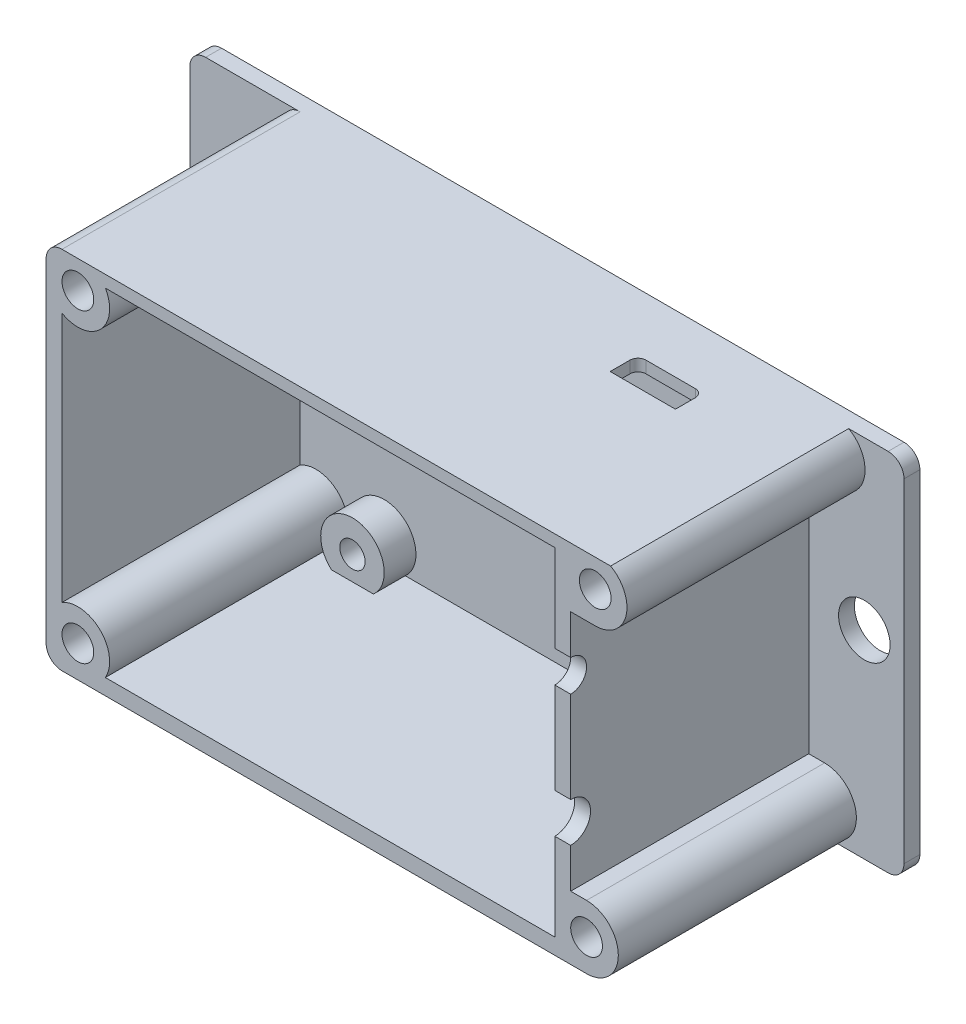
SolidWorks part; units mm, degrees
ref_plane "前视基准面" through (0, 0, 0) normal (0, 0, 1) x (1, 0, 0)
ref_plane "上视基准面" through (0, 0, 0) normal (0, 1, 0) x (1, 0, 0)
ref_plane "右视基准面" through (0, 0, 0) normal (1, 0, 0) x (0, 0, -1)
sketch "Model" plane through (0, 0, 0) normal (0, 0, 1) x (1, 0, 0)
  line L0 (0, 2.26) -> (0, 39.4058)
  line L1 (2.4326, 41.5) -> (50.1564, 41.5)
  line L2 (52.5, 39.422) -> (52.5, 2.28)
  line L3 (50.22, 0) -> (2.26, 0)
  line L4 (0.57, 8.85) -> (-6.93, 8.85)
  line L5 (-6.93, 8.85) -> (-6.93, 24.85)
  line L6 (-6.93, 24.85) -> (0.57, 24.85)
  line L7 (16.57, 8.85) -> (17.57, 8.85)
  line L8 (17.57, 8.85) -> (17.57, 10.85)
  line L9 (17.57, 22.85) -> (17.57, 24.85)
  line L10 (17.57, 24.85) -> (16.57, 24.85)
  line L11 (24.196, 8.775) -> (23.307, 8.775)
  line L12 (22.926, 9.156) -> (22.926, 9.664)
  line L13 (23.307, 10.045) -> (24.196, 10.045)
  line L14 (24.704, 10.045) -> (25.593, 10.045)
  line L15 (25.974, 9.664) -> (25.974, 9.156)
  line L16 (25.593, 8.775) -> (24.704, 8.775)
  line L17 (34.756, 17.315) -> (33.867, 17.315)
  line L18 (33.486, 17.696) -> (33.486, 18.204)
  line L19 (33.867, 18.585) -> (34.756, 18.585)
  line L20 (35.264, 18.585) -> (36.153, 18.585)
  line L21 (36.534, 18.204) -> (36.534, 17.696)
  line L22 (36.153, 17.315) -> (35.264, 17.315)
  line L23 (16.835, 4.806) -> (16.835, 3.917)
  line L24 (16.454, 3.536) -> (15.946, 3.536)
  line L25 (15.565, 3.917) -> (15.565, 4.806)
  line L26 (15.565, 5.314) -> (15.565, 6.203)
  line L27 (15.946, 6.584) -> (16.454, 6.584)
  line L28 (16.835, 6.203) -> (16.835, 5.314)
  line L29 (26.454, 3.425) -> (27.343, 3.425)
  line L30 (27.724, 3.044) -> (27.724, 2.536)
  line L31 (27.343, 2.155) -> (26.454, 2.155)
  line L32 (25.946, 2.155) -> (25.057, 2.155)
  line L33 (24.676, 2.536) -> (24.676, 3.044)
  line L34 (25.057, 3.425) -> (25.946, 3.425)
  line L35 (18.255, 4.756) -> (18.255, 3.867)
  line L36 (17.874, 3.486) -> (17.366, 3.486)
  line L37 (16.985, 3.867) -> (16.985, 4.756)
  line L38 (16.985, 5.264) -> (16.985, 6.153)
  line L39 (17.366, 6.534) -> (17.874, 6.534)
  line L40 (18.255, 6.153) -> (18.255, 5.264)
  line L41 (12.8, 35.75) -> (12.8, 38.8)
  line L42 (12.8, 38.8) -> (14.05, 39.95)
  line L43 (14.05, 39.95) -> (16.45, 39.95)
  line L44 (16.45, 39.95) -> (17.6, 38.9)
  line L45 (17.6, 38.9) -> (17.6, 35.7)
  line L46 (17.6, 35.7) -> (16.45, 34.65)
  line L47 (16.45, 34.65) -> (14, 34.65)
  line L48 (14, 34.65) -> (12.8, 35.75)
  line L49 (3.87, 5.53) -> (6.67, 5.53)
  line L50 (6.67, 5.53) -> (6.67, 4.13)
  line L51 (6.67, 4.13) -> (3.87, 4.13)
  line L52 (3.87, 4.13) -> (3.87, 5.53)
  line L53 (20.8, 6.56) -> (20.8, 9.36)
  line L54 (20.8, 9.36) -> (22.2, 9.36)
  line L55 (22.2, 9.36) -> (22.2, 6.56)
  line L56 (22.2, 6.56) -> (20.8, 6.56)
  line L57 (8.21, 6.97) -> (8.21, 4.17)
  line L58 (8.21, 4.17) -> (6.81, 4.17)
  line L59 (6.81, 4.17) -> (6.81, 6.97)
  line L60 (6.81, 6.97) -> (8.21, 6.97)
  line L61 (10.82, 29.94) -> (10.82, 27.14)
  line L62 (10.82, 27.14) -> (9.42, 27.14)
  line L63 (9.42, 27.14) -> (9.42, 29.94)
  line L64 (9.42, 29.94) -> (10.82, 29.94)
  line L65 (33.69, 12.87) -> (30.89, 12.87)
  line L66 (30.89, 12.87) -> (30.89, 14.27)
  line L67 (30.89, 14.27) -> (33.69, 14.27)
  line L68 (33.69, 14.27) -> (33.69, 12.87)
  line L69 (14.93, 29.94) -> (14.93, 27.14)
  line L70 (14.93, 27.14) -> (13.53, 27.14)
  line L71 (13.53, 27.14) -> (13.53, 29.94)
  line L72 (13.53, 29.94) -> (14.93, 29.94)
  line L73 (26.13, 4.53) -> (26.37, 4.53)
  line L74 (26.37, 4.53) -> (26.37, 7.36)
  line L75 (26.37, 7.36) -> (26.13, 7.36)
  line L76 (22.89, 4.53) -> (22.6, 4.53)
  line L77 (22.6, 4.53) -> (22.6, 7.37)
  line L78 (22.6, 7.37) -> (22.87, 7.37)
  line L79 (1.79, 29.79) -> (6.87, 29.79)
  line L80 (6.87, 29.79) -> (6.87, 27.25)
  line L81 (6.87, 27.25) -> (1.79, 27.25)
  line L82 (1.79, 27.25) -> (1.79, 29.79)
  line L83 (29.996, 38.955) -> (29.107, 38.955)
  line L84 (28.726, 39.336) -> (28.726, 39.844)
  line L85 (29.107, 40.225) -> (29.996, 40.225)
  line L86 (30.504, 40.225) -> (31.393, 40.225)
  line L87 (31.774, 39.844) -> (31.774, 39.336)
  line L88 (31.393, 38.955) -> (30.504, 38.955)
  line L89 (35.825, 11.706) -> (35.825, 10.817)
  line L90 (35.444, 10.436) -> (34.936, 10.436)
  line L91 (34.555, 10.817) -> (34.555, 11.706)
  line L92 (34.555, 12.214) -> (34.555, 13.103)
  line L93 (34.936, 13.484) -> (35.444, 13.484)
  line L94 (35.825, 13.103) -> (35.825, 12.214)
  line L95 (31.416, 6.905) -> (30.527, 6.905)
  line L96 (30.146, 7.286) -> (30.146, 7.794)
  line L97 (30.527, 8.175) -> (31.416, 8.175)
  line L98 (31.924, 8.175) -> (32.813, 8.175)
  line L99 (33.194, 7.794) -> (33.194, 7.286)
  line L100 (32.813, 6.905) -> (31.924, 6.905)
  line L101 (27.125, 13.384) -> (27.125, 14.273)
  line L102 (27.506, 14.654) -> (28.014, 14.654)
  line L103 (28.395, 14.273) -> (28.395, 13.384)
  line L104 (28.395, 12.876) -> (28.395, 11.987)
  line L105 (28.014, 11.606) -> (27.506, 11.606)
  line L106 (27.125, 11.987) -> (27.125, 12.876)
  line L107 (2.726, 5.765) -> (1.837, 5.765)
  line L108 (1.456, 6.146) -> (1.456, 6.654)
  line L109 (1.837, 7.035) -> (2.726, 7.035)
  line L110 (3.234, 7.035) -> (4.123, 7.035)
  line L111 (4.504, 6.654) -> (4.504, 6.146)
  line L112 (4.123, 5.765) -> (3.234, 5.765)
  line L113 (38.274, 36.345) -> (39.163, 36.345)
  line L114 (39.544, 35.964) -> (39.544, 35.456)
  line L115 (39.163, 35.075) -> (38.274, 35.075)
  line L116 (37.766, 35.075) -> (36.877, 35.075)
  line L117 (36.496, 35.456) -> (36.496, 35.964)
  line L118 (36.877, 36.345) -> (37.766, 36.345)
  line L119 (35.295, 38.504) -> (35.295, 39.393)
  line L120 (35.676, 39.774) -> (36.184, 39.774)
  line L121 (36.565, 39.393) -> (36.565, 38.504)
  line L122 (36.565, 37.996) -> (36.565, 37.107)
  line L123 (36.184, 36.726) -> (35.676, 36.726)
  line L124 (35.295, 37.107) -> (35.295, 37.996)
  line L125 (31.265, 4.376) -> (31.265, 3.487)
  line L126 (30.884, 3.106) -> (30.376, 3.106)
  line L127 (29.995, 3.487) -> (29.995, 4.376)
  line L128 (29.995, 4.884) -> (29.995, 5.773)
  line L129 (30.376, 6.154) -> (30.884, 6.154)
  line L130 (31.265, 5.773) -> (31.265, 4.884)
  line L131 (33.42, 4.7325) -> (33.42, 6.15)
  line L132 (33.42, 6.15) -> (31.5, 6.15)
  line L133 (31.5, 6.15) -> (31.5, 4.7325)
  line L134 (33.42, 2.8275) -> (33.42, 1.43)
  line L135 (33.42, 1.43) -> (31.5, 1.43)
  line L136 (31.5, 1.43) -> (31.5, 2.8275)
  line L137 (37.99, 12.2925) -> (37.99, 13.71)
  line L138 (37.99, 13.71) -> (36.07, 13.71)
  line L139 (36.07, 13.71) -> (36.07, 12.2925)
  line L140 (37.99, 10.3875) -> (37.99, 8.99)
  line L141 (37.99, 8.99) -> (36.07, 8.99)
  line L142 (36.07, 8.99) -> (36.07, 10.3875)
  line L143 (37.074, 38.3336) -> (37.074, 37.343)
  line L144 (37.582, 36.835) -> (38.6488, 36.835)
  line L145 (39.106, 37.3176) -> (39.106, 38.3336)
  line L146 (37.074, 39.1464) -> (37.074, 40.137)
  line L147 (37.582, 40.645) -> (38.6488, 40.645)
  line L148 (39.106, 40.1624) -> (39.106, 39.1464)
  line L149 (33.975, 16.983) -> (31.689, 16.983)
  line L150 (31.689, 16.983) -> (31.689, 14.697)
  line L151 (31.689, 14.697) -> (33.975, 14.697)
  line L152 (35.245, 16.983) -> (37.15, 16.983)
  line L153 (37.15, 16.983) -> (37.531, 16.602)
  line L154 (37.531, 16.602) -> (37.531, 15.078)
  line L155 (37.531, 15.078) -> (37.15, 14.697)
  line L156 (37.15, 14.697) -> (35.245, 14.697)
  line L157 (21.1, 35.75) -> (21.1, 38.8)
  line L158 (21.1, 38.8) -> (22.35, 39.95)
  line L159 (22.35, 39.95) -> (24.75, 39.95)
  line L160 (24.75, 39.95) -> (25.9, 38.9)
  line L161 (25.9, 38.9) -> (25.9, 35.7)
  line L162 (25.9, 35.7) -> (24.75, 34.65)
  line L163 (24.75, 34.65) -> (22.3, 34.65)
  line L164 (22.3, 34.65) -> (21.1, 35.75)
  line L165 (5.44, 35.75) -> (5.44, 38.8)
  line L166 (5.44, 38.8) -> (6.69, 39.95)
  line L167 (6.69, 39.95) -> (9.09, 39.95)
  line L168 (9.09, 39.95) -> (10.24, 38.9)
  line L169 (10.24, 38.9) -> (10.24, 35.7)
  line L170 (10.24, 35.7) -> (9.09, 34.65)
  line L171 (9.09, 34.65) -> (6.64, 34.65)
  line L172 (6.64, 34.65) -> (5.44, 35.75)
  line L173 (34.57, 3.22) -> (38.57, 3.22)
  line L174 (38.57, 3.22) -> (38.57, 8.72)
  line L175 (38.57, 8.72) -> (34.57, 8.72)
  line L176 (34.57, 8.72) -> (34.57, 3.22)
  line L177 (39.81, 30.07) -> (37.01, 30.07)
  line L178 (37.01, 30.07) -> (37.01, 31.47)
  line L179 (37.01, 31.47) -> (39.81, 31.47)
  line L180 (39.81, 31.47) -> (39.81, 30.07)
  line L181 (28.51, 40.17) -> (28.51, 37.37)
  line L182 (28.51, 37.37) -> (27.11, 37.37)
  line L183 (27.11, 37.37) -> (27.11, 40.17)
  line L184 (27.11, 40.17) -> (28.51, 40.17)
  line L185 (32.06, 40.25) -> (34.86, 40.25)
  line L186 (34.86, 40.25) -> (34.86, 38.85)
  line L187 (34.86, 38.85) -> (32.06, 38.85)
  line L188 (32.06, 38.85) -> (32.06, 40.25)
  line L189 (28.56, 11.71) -> (28.56, 14.51)
  line L190 (28.56, 14.51) -> (29.96, 14.51)
  line L191 (29.96, 14.51) -> (29.96, 11.71)
  line L192 (29.96, 11.71) -> (28.56, 11.71)
  line L193 (25.54, 13.29) -> (25.54, 16.09)
  line L194 (25.54, 16.09) -> (26.94, 16.09)
  line L195 (26.94, 16.09) -> (26.94, 13.29)
  line L196 (26.94, 13.29) -> (25.54, 13.29)
  line L197 (27.11, 11.4) -> (29.91, 11.4)
  line L198 (29.91, 11.4) -> (29.91, 10)
  line L199 (29.91, 10) -> (27.11, 10)
  line L200 (27.11, 10) -> (27.11, 11.4)
  line L201 (29.06, 8.4) -> (26.26, 8.4)
  line L202 (26.26, 8.4) -> (26.26, 9.8)
  line L203 (26.26, 9.8) -> (29.06, 9.8)
  line L204 (29.06, 9.8) -> (29.06, 8.4)
  line L205 (18.53, 32.56) -> (18.53, 29.76)
  line L206 (18.53, 29.76) -> (17.13, 29.76)
  line L207 (17.13, 29.76) -> (17.13, 32.56)
  line L208 (17.13, 32.56) -> (18.53, 32.56)
  line L209 (5.02, 31.95) -> (2.22, 31.95)
  line L210 (2.22, 31.95) -> (2.22, 33.35)
  line L211 (2.22, 33.35) -> (5.02, 33.35)
  line L212 (5.02, 33.35) -> (5.02, 31.95)
  line L213 (9.22, 29.96) -> (9.22, 27.16)
  line L214 (9.22, 27.16) -> (7.82, 27.16)
  line L215 (7.82, 27.16) -> (7.82, 29.96)
  line L216 (7.82, 29.96) -> (9.22, 29.96)
  line L217 (25.54, 18.87) -> (28.34, 18.87)
  line L218 (28.34, 18.87) -> (28.34, 17.47)
  line L219 (28.34, 17.47) -> (25.54, 17.47)
  line L220 (25.54, 17.47) -> (25.54, 18.87)
  line L221 (28.31, 19.13) -> (25.51, 19.13)
  line L222 (25.51, 19.13) -> (25.51, 20.53)
  line L223 (25.51, 20.53) -> (28.31, 20.53)
  line L224 (28.31, 20.53) -> (28.31, 19.13)
  line L225 (8.87, 4.41) -> (8.87, 7.21)
  line L226 (8.87, 7.21) -> (10.27, 7.21)
  line L227 (10.27, 7.21) -> (10.27, 4.41)
  line L228 (10.27, 4.41) -> (8.87, 4.41)
  line L229 (11.05, 4.16) -> (11.05, 6.96)
  line L230 (11.05, 6.96) -> (12.45, 6.96)
  line L231 (12.45, 6.96) -> (12.45, 4.16)
  line L232 (12.45, 4.16) -> (11.05, 4.16)
  line L233 (7.61, 30.34) -> (4.81, 30.34)
  line L234 (4.81, 30.34) -> (4.81, 31.74)
  line L235 (4.81, 31.74) -> (7.61, 31.74)
  line L236 (7.61, 31.74) -> (7.61, 30.34)
  line L237 (4.24, 30.32) -> (1.44, 30.32)
  line L238 (1.44, 30.32) -> (1.44, 31.72)
  line L239 (1.44, 31.72) -> (4.24, 31.72)
  line L240 (4.24, 31.72) -> (4.24, 30.32)
  line L241 (39.81, 31.61) -> (37.01, 31.61)
  line L242 (37.01, 31.61) -> (37.01, 33.01)
  line L243 (37.01, 33.01) -> (39.81, 33.01)
  line L244 (39.81, 33.01) -> (39.81, 31.61)
  line L245 (30.83, 8.94) -> (30.83, 8.7)
  line L246 (30.83, 8.7) -> (33.66, 8.7)
  line L247 (33.66, 8.7) -> (33.66, 8.94)
  line L248 (30.83, 12.18) -> (30.83, 12.47)
  line L249 (30.83, 12.47) -> (33.67, 12.47)
  line L250 (33.67, 12.47) -> (33.67, 12.2)
  line L251 (51.33, 22.79) -> (51.33, 33.29)
  line L252 (51.33, 33.29) -> (45.93, 33.29)
  line L253 (45.93, 33.29) -> (45.93, 22.79)
  line L254 (45.93, 22.79) -> (46.63, 22.09)
  line L255 (46.63, 22.09) -> (50.63, 22.09)
  line L256 (50.63, 22.09) -> (51.33, 22.79)
  line L257 (48.63, 35.31) -> (48.63, 33.278)
  line L258 (49.646, 34.294) -> (47.614, 34.294)
  line L259 (51.38, 7.21) -> (51.38, 17.71)
  line L260 (51.38, 17.71) -> (45.98, 17.71)
  line L261 (45.98, 17.71) -> (45.98, 7.21)
  line L262 (45.98, 7.21) -> (46.68, 6.51)
  line L263 (46.68, 6.51) -> (50.68, 6.51)
  line L264 (50.68, 6.51) -> (51.38, 7.21)
  line L265 (48.68, 19.73) -> (48.68, 17.698)
  line L266 (49.696, 18.714) -> (47.664, 18.714)
  line L267 (31.402, 24.62) -> (31.402, 19.54)
  line L268 (31.402, 19.54) -> (34.958, 19.54)
  line L269 (34.958, 19.54) -> (34.958, 24.62)
  line L270 (34.958, 24.62) -> (31.402, 24.62)
  line L271 (33.942, 24.62) -> (33.942, 24.112)
  line L272 (33.942, 24.112) -> (32.418, 24.112)
  line L273 (32.418, 24.112) -> (32.418, 24.62)
  line L274 (35.323, 25.5545) -> (37.482, 25.5545)
  line L275 (37.482, 25.5545) -> (37.482, 29.7455)
  line L276 (37.482, 29.7455) -> (35.323, 29.7455)
  line L277 (30.497, 25.5545) -> (28.338, 25.5545)
  line L278 (28.338, 25.5545) -> (28.338, 29.7455)
  line L279 (28.338, 29.7455) -> (30.497, 29.7455)
  line L280 (39.675, 36.4523) -> (39.675, 38.9337)
  line L281 (39.675, 38.9337) -> (39.6757, 38.9337)
  line L282 (39.6757, 38.9337) -> (39.6757, 41.34)
  line L283 (39.6757, 41.34) -> (47.0987, 41.34)
  line L284 (47.0987, 41.34) -> (47.0987, 36.4523)
  line L285 (47.0987, 36.4523) -> (39.675, 36.4523)
  line L286 (39.674, 41.32) -> (47.0987, 41.32)
  line L287 (47.0987, 41.32) -> (47.0987, 41.84)
  line L288 (47.0987, 41.84) -> (39.674, 41.84)
  line L289 (39.674, 41.84) -> (39.674, 41.32)
  line L290 (40.55, 41.34) -> (40.12, 41.77)
  line L291 (46.28, 41.37) -> (46.71, 41.8)
  line L292 (35.28, 32.52) -> (35.28, 31.92)
  line L293 (35.28, 31.92) -> (34.88, 31.52)
  line L294 (34.88, 31.52) -> (34.38, 31.52)
  line L295 (34.98, 36.32) -> (34.98, 36.82)
  line L296 (34.98, 36.82) -> (34.48, 36.82)
  line L297 (29.98, 36.32) -> (29.98, 36.82)
  line L298 (29.98, 36.82) -> (30.48, 36.82)
  line L299 (29.98, 32.32) -> (29.98, 31.82)
  line L300 (29.98, 31.82) -> (30.48, 31.82)
  arc A0 (0, 2.26) -> (2.26, 0) centre (2.5947, 2.5947) ccw
  arc A1 (2.4326, 41.5) -> (0, 39.4058) centre (2.365, 39.1186) ccw
  arc A2 (52.5, 39.422) -> (50.1564, 41.5) centre (50.2928, 39.2933) ccw
  arc A3 (50.22, 0) -> (52.5, 2.28) centre (50.2397, 2.2603) ccw
  circle A4 centre (2.26, 0) radius 0.0635
  circle A5 centre (0, 2.26) radius 0.0635
  circle A6 centre (0, 39.4058) radius 0.0635
  circle A7 centre (2.4326, 41.5) radius 0.0635
  circle A8 centre (50.1564, 41.5) radius 0.0635
  circle A9 centre (52.5, 39.422) radius 0.0635
  circle A10 centre (52.5, 2.28) radius 0.0635
  circle A11 centre (2, 39.5) radius 1.1
  circle A12 centre (50.5, 39.5) radius 1.1
  circle A13 centre (50.5, 2) radius 1.1
  circle A14 centre (2, 2) radius 1.1
  circle A15 centre (0.57, 8.85) radius 0.0635
  circle A16 centre (-6.93, 8.85) radius 0.0635
  circle A17 centre (-6.93, 24.85) radius 0.0635
  circle A18 centre (0.57, 24.85) radius 0.0635
  circle A19 centre (16.57, 8.85) radius 0.0635
  circle A20 centre (17.57, 8.85) radius 0.0635
  circle A21 centre (17.57, 10.85) radius 0.0635
  circle A22 centre (17.57, 22.85) radius 0.0635
  circle A23 centre (17.57, 24.85) radius 0.0635
  circle A24 centre (16.57, 24.85) radius 0.0635
  circle A25 centre (1.57, 7.55) radius 0.3606
  arc A26 (22.926, 9.156) -> (23.307, 8.775) centre (23.307, 9.156) ccw
  arc A27 (23.307, 10.045) -> (22.926, 9.664) centre (23.307, 9.664) ccw
  circle A28 centre (24.196, 8.775) radius 0.025
  circle A29 centre (23.307, 8.775) radius 0.025
  arc A30 (25.974, 9.664) -> (25.593, 10.045) centre (25.593, 9.664) ccw
  arc A31 (25.593, 8.775) -> (25.974, 9.156) centre (25.593, 9.156) ccw
  circle A32 centre (24.704, 10.045) radius 0.025
  circle A33 centre (25.593, 10.045) radius 0.025
  arc A34 (33.486, 17.696) -> (33.867, 17.315) centre (33.867, 17.696) ccw
  arc A35 (33.867, 18.585) -> (33.486, 18.204) centre (33.867, 18.204) ccw
  circle A36 centre (34.756, 17.315) radius 0.025
  circle A37 centre (33.867, 17.315) radius 0.025
  arc A38 (36.534, 18.204) -> (36.153, 18.585) centre (36.153, 18.204) ccw
  arc A39 (36.153, 17.315) -> (36.534, 17.696) centre (36.153, 17.696) ccw
  circle A40 centre (35.264, 18.585) radius 0.025
  circle A41 centre (36.153, 18.585) radius 0.025
  arc A42 (16.454, 3.536) -> (16.835, 3.917) centre (16.454, 3.917) ccw
  arc A43 (15.565, 3.917) -> (15.946, 3.536) centre (15.946, 3.917) ccw
  circle A44 centre (16.835, 4.806) radius 0.025
  circle A45 centre (16.835, 3.917) radius 0.025
  arc A46 (15.946, 6.584) -> (15.565, 6.203) centre (15.946, 6.203) ccw
  arc A47 (16.835, 6.203) -> (16.454, 6.584) centre (16.454, 6.203) ccw
  circle A48 centre (15.565, 5.314) radius 0.025
  circle A49 centre (15.565, 6.203) radius 0.025
  arc A50 (27.724, 3.044) -> (27.343, 3.425) centre (27.343, 3.044) ccw
  arc A51 (27.343, 2.155) -> (27.724, 2.536) centre (27.343, 2.536) ccw
  circle A52 centre (26.454, 3.425) radius 0.025
  circle A53 centre (27.343, 3.425) radius 0.025
  arc A54 (24.676, 2.536) -> (25.057, 2.155) centre (25.057, 2.536) ccw
  arc A55 (25.057, 3.425) -> (24.676, 3.044) centre (25.057, 3.044) ccw
  circle A56 centre (25.946, 2.155) radius 0.025
  circle A57 centre (25.057, 2.155) radius 0.025
  arc A58 (17.874, 3.486) -> (18.255, 3.867) centre (17.874, 3.867) ccw
  arc A59 (16.985, 3.867) -> (17.366, 3.486) centre (17.366, 3.867) ccw
  circle A60 centre (18.255, 4.756) radius 0.025
  circle A61 centre (18.255, 3.867) radius 0.025
  arc A62 (17.366, 6.534) -> (16.985, 6.153) centre (17.366, 6.153) ccw
  arc A63 (18.255, 6.153) -> (17.874, 6.534) centre (17.874, 6.153) ccw
  circle A64 centre (16.985, 5.264) radius 0.025
  circle A65 centre (16.985, 6.153) radius 0.025
  circle A66 centre (12.8, 35.75) radius 0.0375
  circle A67 centre (12.8, 38.8) radius 0.0375
  circle A68 centre (14.05, 39.95) radius 0.0375
  circle A69 centre (16.45, 39.95) radius 0.0375
  circle A70 centre (17.6, 38.9) radius 0.0375
  circle A71 centre (17.6, 35.7) radius 0.0375
  circle A72 centre (16.45, 34.65) radius 0.0375
  circle A73 centre (14, 34.65) radius 0.0375
  circle A74 centre (15.2, 37.3) radius 1.5
  circle A75 centre (15.2, 37.3) radius 0.7566
  circle A76 centre (3.87, 5.53) radius 0.0375
  circle A77 centre (6.67, 5.53) radius 0.0375
  circle A78 centre (6.67, 4.13) radius 0.0375
  circle A79 centre (3.87, 4.13) radius 0.0375
  circle A80 centre (20.8, 6.56) radius 0.0375
  circle A81 centre (20.8, 9.36) radius 0.0375
  circle A82 centre (22.2, 9.36) radius 0.0375
  circle A83 centre (22.2, 6.56) radius 0.0375
  circle A84 centre (8.21, 6.97) radius 0.0375
  circle A85 centre (8.21, 4.17) radius 0.0375
  circle A86 centre (6.81, 4.17) radius 0.0375
  circle A87 centre (6.81, 6.97) radius 0.0375
  circle A88 centre (10.82, 29.94) radius 0.0375
  circle A89 centre (10.82, 27.14) radius 0.0375
  circle A90 centre (9.42, 27.14) radius 0.0375
  circle A91 centre (9.42, 29.94) radius 0.0375
  circle A92 centre (33.69, 12.87) radius 0.0375
  circle A93 centre (30.89, 12.87) radius 0.0375
  circle A94 centre (30.89, 14.27) radius 0.0375
  circle A95 centre (33.69, 14.27) radius 0.0375
  circle A96 centre (14.93, 29.94) radius 0.0375
  circle A97 centre (14.93, 27.14) radius 0.0375
  circle A98 centre (13.53, 27.14) radius 0.0375
  circle A99 centre (13.53, 29.94) radius 0.0375
  circle A100 centre (26.13, 4.53) radius 0.05
  circle A101 centre (26.37, 4.53) radius 0.05
  circle A102 centre (26.37, 7.36) radius 0.05
  circle A103 centre (26.13, 7.36) radius 0.05
  circle A104 centre (22.89, 4.53) radius 0.05
  circle A105 centre (22.6, 4.53) radius 0.05
  circle A106 centre (22.6, 7.37) radius 0.05
  circle A107 centre (22.87, 7.37) radius 0.05
  circle A108 centre (1.79, 29.79) radius 0.0635
  circle A109 centre (6.87, 29.79) radius 0.0635
  circle A110 centre (6.87, 27.25) radius 0.0635
  circle A111 centre (1.79, 27.25) radius 0.0635
  arc A112 (28.726, 39.336) -> (29.107, 38.955) centre (29.107, 39.336) ccw
  arc A113 (29.107, 40.225) -> (28.726, 39.844) centre (29.107, 39.844) ccw
  circle A114 centre (29.996, 38.955) radius 0.025
  circle A115 centre (29.107, 38.955) radius 0.025
  arc A116 (31.774, 39.844) -> (31.393, 40.225) centre (31.393, 39.844) ccw
  arc A117 (31.393, 38.955) -> (31.774, 39.336) centre (31.393, 39.336) ccw
  circle A118 centre (30.504, 40.225) radius 0.025
  circle A119 centre (31.393, 40.225) radius 0.025
  arc A120 (35.444, 10.436) -> (35.825, 10.817) centre (35.444, 10.817) ccw
  arc A121 (34.555, 10.817) -> (34.936, 10.436) centre (34.936, 10.817) ccw
  circle A122 centre (35.825, 11.706) radius 0.025
  circle A123 centre (35.825, 10.817) radius 0.025
  arc A124 (34.936, 13.484) -> (34.555, 13.103) centre (34.936, 13.103) ccw
  arc A125 (35.825, 13.103) -> (35.444, 13.484) centre (35.444, 13.103) ccw
  circle A126 centre (34.555, 12.214) radius 0.025
  circle A127 centre (34.555, 13.103) radius 0.025
  arc A128 (30.146, 7.286) -> (30.527, 6.905) centre (30.527, 7.286) ccw
  arc A129 (30.527, 8.175) -> (30.146, 7.794) centre (30.527, 7.794) ccw
  circle A130 centre (31.416, 6.905) radius 0.025
  circle A131 centre (30.527, 6.905) radius 0.025
  arc A132 (33.194, 7.794) -> (32.813, 8.175) centre (32.813, 7.794) ccw
  arc A133 (32.813, 6.905) -> (33.194, 7.286) centre (32.813, 7.286) ccw
  circle A134 centre (31.924, 8.175) radius 0.025
  circle A135 centre (32.813, 8.175) radius 0.025
  arc A136 (27.506, 14.654) -> (27.125, 14.273) centre (27.506, 14.273) ccw
  arc A137 (28.395, 14.273) -> (28.014, 14.654) centre (28.014, 14.273) ccw
  circle A138 centre (27.125, 13.384) radius 0.025
  circle A139 centre (27.125, 14.273) radius 0.025
  arc A140 (28.014, 11.606) -> (28.395, 11.987) centre (28.014, 11.987) ccw
  arc A141 (27.125, 11.987) -> (27.506, 11.606) centre (27.506, 11.987) ccw
  circle A142 centre (28.395, 12.876) radius 0.025
  circle A143 centre (28.395, 11.987) radius 0.025
  arc A144 (1.456, 6.146) -> (1.837, 5.765) centre (1.837, 6.146) ccw
  arc A145 (1.837, 7.035) -> (1.456, 6.654) centre (1.837, 6.654) ccw
  circle A146 centre (2.726, 5.765) radius 0.025
  circle A147 centre (1.837, 5.765) radius 0.025
  arc A148 (4.504, 6.654) -> (4.123, 7.035) centre (4.123, 6.654) ccw
  arc A149 (4.123, 5.765) -> (4.504, 6.146) centre (4.123, 6.146) ccw
  circle A150 centre (3.234, 7.035) radius 0.025
  circle A151 centre (4.123, 7.035) radius 0.025
  arc A152 (39.544, 35.964) -> (39.163, 36.345) centre (39.163, 35.964) ccw
  arc A153 (39.163, 35.075) -> (39.544, 35.456) centre (39.163, 35.456) ccw
  circle A154 centre (38.274, 36.345) radius 0.025
  circle A155 centre (39.163, 36.345) radius 0.025
  arc A156 (36.496, 35.456) -> (36.877, 35.075) centre (36.877, 35.456) ccw
  arc A157 (36.877, 36.345) -> (36.496, 35.964) centre (36.877, 35.964) ccw
  circle A158 centre (37.766, 35.075) radius 0.025
  circle A159 centre (36.877, 35.075) radius 0.025
  arc A160 (35.676, 39.774) -> (35.295, 39.393) centre (35.676, 39.393) ccw
  arc A161 (36.565, 39.393) -> (36.184, 39.774) centre (36.184, 39.393) ccw
  circle A162 centre (35.295, 38.504) radius 0.025
  circle A163 centre (35.295, 39.393) radius 0.025
  arc A164 (36.184, 36.726) -> (36.565, 37.107) centre (36.184, 37.107) ccw
  arc A165 (35.295, 37.107) -> (35.676, 36.726) centre (35.676, 37.107) ccw
  circle A166 centre (36.565, 37.996) radius 0.025
  circle A167 centre (36.565, 37.107) radius 0.025
  arc A168 (30.884, 3.106) -> (31.265, 3.487) centre (30.884, 3.487) ccw
  arc A169 (29.995, 3.487) -> (30.376, 3.106) centre (30.376, 3.487) ccw
  circle A170 centre (31.265, 4.376) radius 0.025
  circle A171 centre (31.265, 3.487) radius 0.025
  arc A172 (30.376, 6.154) -> (29.995, 5.773) centre (30.376, 5.773) ccw
  arc A173 (31.265, 5.773) -> (30.884, 6.154) centre (30.884, 5.773) ccw
  circle A174 centre (29.995, 4.884) radius 0.025
  circle A175 centre (29.995, 5.773) radius 0.025
  circle A176 centre (33.42, 4.7325) radius 0.0635
  circle A177 centre (33.42, 6.15) radius 0.0635
  circle A178 centre (31.5, 6.15) radius 0.0635
  circle A179 centre (31.5, 4.7325) radius 0.0635
  circle A180 centre (33.42, 2.8275) radius 0.0635
  circle A181 centre (33.42, 1.43) radius 0.0635
  circle A182 centre (31.5, 1.43) radius 0.0635
  circle A183 centre (31.5, 2.8275) radius 0.0635
  circle A184 centre (37.99, 12.2925) radius 0.0635
  circle A185 centre (37.99, 13.71) radius 0.0635
  circle A186 centre (36.07, 13.71) radius 0.0635
  circle A187 centre (36.07, 12.2925) radius 0.0635
  circle A188 centre (37.99, 10.3875) radius 0.0635
  circle A189 centre (37.99, 8.99) radius 0.0635
  circle A190 centre (36.07, 8.99) radius 0.0635
  circle A191 centre (36.07, 10.3875) radius 0.0635
  arc A192 (37.074, 37.343) -> (37.582, 36.835) centre (37.582, 37.343) ccw
  arc A193 (38.6488, 36.835) -> (39.106, 37.3176) centre (38.6361, 37.3049) ccw
  circle A194 centre (37.074, 38.3336) radius 0.0254
  circle A195 centre (37.074, 37.343) radius 0.0254
  arc A196 (37.582, 40.645) -> (37.074, 40.137) centre (37.582, 40.137) ccw
  arc A197 (39.106, 40.1624) -> (38.6488, 40.645) centre (38.6361, 40.1751) ccw
  circle A198 centre (37.074, 39.1464) radius 0.0254
  circle A199 centre (37.074, 40.137) radius 0.0254
  circle A200 centre (33.975, 16.983) radius 0.0635
  circle A201 centre (31.689, 16.983) radius 0.0635
  circle A202 centre (31.689, 14.697) radius 0.0635
  circle A203 centre (33.975, 14.697) radius 0.0635
  circle A204 centre (35.245, 16.983) radius 0.0635
  circle A205 centre (37.15, 16.983) radius 0.0635
  circle A206 centre (37.531, 16.602) radius 0.0635
  circle A207 centre (37.531, 15.078) radius 0.0635
  circle A208 centre (37.15, 14.697) radius 0.0635
  circle A209 centre (35.245, 14.697) radius 0.0635
  circle A210 centre (21.1, 35.75) radius 0.0375
  circle A211 centre (21.1, 38.8) radius 0.0375
  circle A212 centre (22.35, 39.95) radius 0.0375
  circle A213 centre (24.75, 39.95) radius 0.0375
  circle A214 centre (25.9, 38.9) radius 0.0375
  circle A215 centre (25.9, 35.7) radius 0.0375
  circle A216 centre (24.75, 34.65) radius 0.0375
  circle A217 centre (22.3, 34.65) radius 0.0375
  circle A218 centre (23.5, 37.3) radius 1.5
  circle A219 centre (23.5, 37.3) radius 0.7566
  circle A220 centre (5.44, 35.75) radius 0.0375
  circle A221 centre (5.44, 38.8) radius 0.0375
  circle A222 centre (6.69, 39.95) radius 0.0375
  circle A223 centre (9.09, 39.95) radius 0.0375
  circle A224 centre (10.24, 38.9) radius 0.0375
  circle A225 centre (10.24, 35.7) radius 0.0375
  circle A226 centre (9.09, 34.65) radius 0.0375
  circle A227 centre (6.64, 34.65) radius 0.0375
  circle A228 centre (7.84, 37.3) radius 1.5
  circle A229 centre (7.84, 37.3) radius 0.7566
  circle A230 centre (34.57, 3.22) radius 0.0381
  circle A231 centre (38.57, 3.22) radius 0.0381
  circle A232 centre (38.57, 8.72) radius 0.0381
  circle A233 centre (34.57, 8.72) radius 0.0381
  circle A234 centre (39.81, 30.07) radius 0.0375
  circle A235 centre (37.01, 30.07) radius 0.0375
  circle A236 centre (37.01, 31.47) radius 0.0375
  circle A237 centre (39.81, 31.47) radius 0.0375
  circle A238 centre (28.51, 40.17) radius 0.0375
  circle A239 centre (28.51, 37.37) radius 0.0375
  circle A240 centre (27.11, 37.37) radius 0.0375
  circle A241 centre (27.11, 40.17) radius 0.0375
  circle A242 centre (32.06, 40.25) radius 0.0375
  circle A243 centre (34.86, 40.25) radius 0.0375
  circle A244 centre (34.86, 38.85) radius 0.0375
  circle A245 centre (32.06, 38.85) radius 0.0375
  circle A246 centre (28.56, 11.71) radius 0.0375
  circle A247 centre (28.56, 14.51) radius 0.0375
  circle A248 centre (29.96, 14.51) radius 0.0375
  circle A249 centre (29.96, 11.71) radius 0.0375
  circle A250 centre (25.54, 13.29) radius 0.0375
  circle A251 centre (25.54, 16.09) radius 0.0375
  circle A252 centre (26.94, 16.09) radius 0.0375
  circle A253 centre (26.94, 13.29) radius 0.0375
  circle A254 centre (27.11, 11.4) radius 0.0375
  circle A255 centre (29.91, 11.4) radius 0.0375
  circle A256 centre (29.91, 10) radius 0.0375
  circle A257 centre (27.11, 10) radius 0.0375
  circle A258 centre (29.06, 8.4) radius 0.0375
  circle A259 centre (26.26, 8.4) radius 0.0375
  circle A260 centre (26.26, 9.8) radius 0.0375
  circle A261 centre (29.06, 9.8) radius 0.0375
  circle A262 centre (18.53, 32.56) radius 0.0375
  circle A263 centre (18.53, 29.76) radius 0.0375
  circle A264 centre (17.13, 29.76) radius 0.0375
  circle A265 centre (17.13, 32.56) radius 0.0375
  circle A266 centre (5.02, 31.95) radius 0.0375
  circle A267 centre (2.22, 31.95) radius 0.0375
  circle A268 centre (2.22, 33.35) radius 0.0375
  circle A269 centre (5.02, 33.35) radius 0.0375
  circle A270 centre (9.22, 29.96) radius 0.0375
  circle A271 centre (9.22, 27.16) radius 0.0375
  circle A272 centre (7.82, 27.16) radius 0.0375
  circle A273 centre (7.82, 29.96) radius 0.0375
  circle A274 centre (25.54, 18.87) radius 0.0375
  circle A275 centre (28.34, 18.87) radius 0.0375
  circle A276 centre (28.34, 17.47) radius 0.0375
  circle A277 centre (25.54, 17.47) radius 0.0375
  circle A278 centre (28.31, 19.13) radius 0.0375
  circle A279 centre (25.51, 19.13) radius 0.0375
  circle A280 centre (25.51, 20.53) radius 0.0375
  circle A281 centre (28.31, 20.53) radius 0.0375
  circle A282 centre (8.87, 4.41) radius 0.0375
  circle A283 centre (8.87, 7.21) radius 0.0375
  circle A284 centre (10.27, 7.21) radius 0.0375
  circle A285 centre (10.27, 4.41) radius 0.0375
  circle A286 centre (11.05, 4.16) radius 0.0375
  circle A287 centre (11.05, 6.96) radius 0.0375
  circle A288 centre (12.45, 6.96) radius 0.0375
  circle A289 centre (12.45, 4.16) radius 0.0375
  circle A290 centre (7.61, 30.34) radius 0.0375
  circle A291 centre (4.81, 30.34) radius 0.0375
  circle A292 centre (4.81, 31.74) radius 0.0375
  circle A293 centre (7.61, 31.74) radius 0.0375
  circle A294 centre (4.24, 30.32) radius 0.0375
  circle A295 centre (1.44, 30.32) radius 0.0375
  circle A296 centre (1.44, 31.72) radius 0.0375
  circle A297 centre (4.24, 31.72) radius 0.0375
  circle A298 centre (39.81, 31.61) radius 0.0375
  circle A299 centre (37.01, 31.61) radius 0.0375
  circle A300 centre (37.01, 33.01) radius 0.0375
  circle A301 centre (39.81, 33.01) radius 0.0375
  circle A302 centre (30.83, 8.94) radius 0.05
  circle A303 centre (30.83, 8.7) radius 0.05
  circle A304 centre (33.66, 8.7) radius 0.05
  circle A305 centre (33.66, 8.94) radius 0.05
  circle A306 centre (30.83, 12.18) radius 0.05
  circle A307 centre (30.83, 12.47) radius 0.05
  circle A308 centre (33.67, 12.47) radius 0.05
  circle A309 centre (33.67, 12.2) radius 0.05
  circle A310 centre (33.43, 8.97) radius 0.2343
  circle A311 centre (51.33, 22.79) radius 0.0635
  circle A312 centre (51.33, 33.29) radius 0.0635
  circle A313 centre (45.93, 33.29) radius 0.0635
  circle A314 centre (45.93, 22.79) radius 0.0635
  circle A315 centre (46.63, 22.09) radius 0.0635
  circle A316 centre (50.63, 22.09) radius 0.0635
  circle A317 centre (48.63, 35.31) radius 0.0635
  circle A318 centre (48.63, 33.278) radius 0.0635
  circle A319 centre (49.646, 34.294) radius 0.0635
  circle A320 centre (47.614, 34.294) radius 0.0635
  circle A321 centre (51.38, 7.21) radius 0.0635
  circle A322 centre (51.38, 17.71) radius 0.0635
  circle A323 centre (45.98, 17.71) radius 0.0635
  circle A324 centre (45.98, 7.21) radius 0.0635
  circle A325 centre (46.68, 6.51) radius 0.0635
  circle A326 centre (50.68, 6.51) radius 0.0635
  circle A327 centre (48.68, 19.73) radius 0.0635
  circle A328 centre (48.68, 17.698) radius 0.0635
  circle A329 centre (49.696, 18.714) radius 0.0635
  circle A330 centre (47.664, 18.714) radius 0.0635
  circle A331 centre (31.402, 24.62) radius 0.0635
  circle A332 centre (31.402, 19.54) radius 0.0635
  circle A333 centre (34.958, 19.54) radius 0.0635
  circle A334 centre (34.958, 24.62) radius 0.0635
  circle A335 centre (30.132, 24.874) radius 0.1778
  circle A336 centre (33.942, 24.62) radius 0.0635
  circle A337 centre (33.942, 24.112) radius 0.0635
  circle A338 centre (32.418, 24.112) radius 0.0635
  circle A339 centre (32.418, 24.62) radius 0.0635
  circle A340 centre (35.323, 25.5545) radius 0.0635
  circle A341 centre (37.482, 25.5545) radius 0.0635
  circle A342 centre (37.482, 29.7455) radius 0.0635
  circle A343 centre (35.323, 29.7455) radius 0.0635
  circle A344 centre (30.497, 25.5545) radius 0.0635
  circle A345 centre (28.338, 25.5545) radius 0.0635
  circle A346 centre (28.338, 29.7455) radius 0.0635
  circle A347 centre (30.497, 29.7455) radius 0.0635
  circle A348 centre (39.675, 36.4523) radius 0.0375
  circle A349 centre (39.675, 38.9337) radius 0.0375
  circle A350 centre (39.6757, 38.9337) radius 0.0375
  circle A351 centre (39.6757, 41.34) radius 0.0375
  circle A352 centre (47.0987, 41.34) radius 0.0375
  circle A353 centre (47.0987, 36.4523) radius 0.0375
  circle A354 centre (39.674, 41.32) radius 0.0375
  circle A355 centre (47.0987, 41.32) radius 0.0375
  circle A356 centre (47.0987, 41.84) radius 0.0375
  circle A357 centre (39.674, 41.84) radius 0.0375
  circle A358 centre (40.55, 41.34) radius 0.0375
  circle A359 centre (40.12, 41.77) radius 0.0375
  circle A360 centre (46.28, 41.37) radius 0.0375
  circle A361 centre (46.71, 41.8) radius 0.0375
  circle A362 centre (35.28, 32.52) radius 0.05
  circle A363 centre (35.28, 31.92) radius 0.05
  circle A364 centre (34.88, 31.52) radius 0.05
  circle A365 centre (34.38, 31.52) radius 0.05
  circle A366 centre (34.98, 36.32) radius 0.05
  circle A367 centre (34.98, 36.82) radius 0.05
  circle A368 centre (34.48, 36.82) radius 0.05
  circle A369 centre (29.98, 36.32) radius 0.05
  circle A370 centre (29.98, 36.82) radius 0.05
  circle A371 centre (30.48, 36.82) radius 0.05
  circle A372 centre (29.98, 32.32) radius 0.05
  circle A373 centre (29.98, 31.82) radius 0.05
  circle A374 centre (30.48, 31.82) radius 0.05
sketch "草图2" plane through (0, 0, 0) normal (0, 0, 1) x (1, 0, 0)
  line L10 (-6.6015, -1) -> (53.5, -1)
  line L11 (53.5, 41.501) -> (53.5, -1)
  line L18 (-8.6015, -3) -> (0, -3)
  line L19 (0, -3) -> (55.5, -3)
  line L20 (55.5, 43.001) -> (55.5, -3)
  line L23 (0, 42.501) -> (53.5, 42.501) construction
  line L24 (0, 42.501) -> (-10.6015, 42.501) construction
  line L25 (0, 43.001) -> (55.5, 43.001)
  line L26 (0, 43.001) -> (-8.6015, 43.001)
  line L31 (-10.6015, 42.501) -> (-10.6015, -1) construction
  line L32 (53.5, 42.501) -> (53.5, -1) construction
  line L33 (-12.6015, 44.501) -> (-12.6015, -3) construction
  line L34 (0, 44.501) -> (-12.6015, 44.501) construction
  line L35 (0, 44.501) -> (55.5, 44.501) construction
  line L36 (55.5, 44.501) -> (55.5, -3) construction
  line L37 (-8.6015, 43.001) -> (-20.5, 43.001)
  line L38 (-22.5, 41.001) -> (-22.5, -1)
  line L39 (-20.5, -3) -> (-8.6015, -3)
  line L40 (55.5, 43.001) -> (65.5, 43.001)
  line L41 (67.5, 41.001) -> (67.5, -1)
  line L42 (65.5, -3) -> (55.5, -3)
  line L43 (52.5, 39.422) -> (52.5, 2.28) construction
  line L44 (-17.5, 22) -> (62.5, 22) construction
  line L45 (-10.6015, -1) -> (0, -1) construction
  line L46 (-8.6015, 39.501) -> (58.5907, 39.501) construction
  line L47 (-8.6015, 1) -> (61.3406, 1) construction
  line L48 (57.5, 5) -> (55.5, 5)
  line L49 (58.5907, 35.501) -> (55.5, 35.501)
  line L50 (-10.6015, 41.001) -> (-10.6015, -1)
  line L51 (-8.6015, 39.501) -> (-8.6015, 1)
  line L52 (0, -1) -> (53.5, -1) construction
  line L53 (-8.6015, 43.001) -> (-8.6015, -3) construction
  line L54 (-10.6015, 43.001) -> (-10.6015, -3) construction
  line L55 (-12.6015, -3) -> (0, -3) construction
  line L56 (-6.6015, 41.501) -> (53.5, 41.501)
  circle A0 centre (2, 39.5) radius 1.1 construction
  circle A1 centre (50.5, 39.5) radius 1.1 construction
  circle A2 centre (50.5, 2) radius 1.1 construction
  circle A3 centre (2, 2) radius 1.1 construction
  circle A4 centre (23.5, 37.3) radius 2.8844 construction
  circle A5 centre (-17.5, 22) radius 3.25
  circle A6 centre (62.5, 22) radius 3.25
  arc A7 (65.5, -3) -> (67.5, -1) centre (65.5, -1) ccw
  arc A8 (67.5, 41.001) -> (65.5, 43.001) centre (65.5, 41.001) ccw
  arc A9 (-20.5, 43.001) -> (-22.5, 41.001) centre (-20.5, 41.001) ccw
  arc A10 (-22.5, -1) -> (-20.5, -3) centre (-20.5, -1) ccw
  circle A11 centre (2, 39.5) radius 1.6
  circle A12 centre (50.5, 39.5) radius 1.6
  circle A13 centre (2, 2) radius 1.6
  circle A14 centre (50.5, 2) radius 1.6
  arc A15 (-0.8728, 41.501) -> (4.8728, 41.501) centre (2, 39.5) ccw
  arc A16 (47.6272, 41.501) -> (53.5, 37.6954) centre (50.5, 39.5) ccw
  arc A19 (4.6458, -1) -> (-0.6458, -1) centre (2, 2) ccw
  arc A20 (53.5, 4.6458) -> (47.8542, -1) centre (50.5, 2) ccw
  circle A21 centre (-6.6015, 39.501) radius 2
  arc A22 (-8.6015, 36.0369) -> (-3.1374, 41.501) centre (-6.6015, 39.501) ccw
  circle A23 centre (-6.6015, 1) radius 2
  arc A24 (-3.1374, -1) -> (-8.6015, 4.4641) centre (-6.6015, 1) ccw
  circle A25 centre (58.5907, 39.501) radius 2
  arc A26 (58.5907, 35.501) -> (60.5272, 43.001) centre (58.5907, 39.501) ccw
  circle A27 centre (57.5, 1) radius 2
  arc A28 (57.5, -3) -> (57.5, 5) centre (57.5, 1) ccw
  arc A29 (-8.6015, 43.001) -> (-10.6015, 41.001) centre (-8.6015, 41.001) ccw
  arc A30 (-8.6015, -3) -> (-10.6015, -1) centre (-8.6015, -1) cw
  dimension "D1" = 2.2
  dimension "D5" = 6.5
  dimension "D6" = 6.5
  dimension "D11" = 2
  dimension "D12" = 4
  dimension "D13" = 8
  dimension "D14" = 4
  dimension "D15" = 2
  dimension "D16" = 4
  dimension "D17" = 8
  dimension "D18" = 4
  dimension "D19" = 3.2
  dimension "D20" = 3.2
  dimension "D21" = 3.2
  dimension "D22" = 3.2
  dimension "D24" = 2
  dimension "D2" = 80
  dimension "D7" = 10
  dimension "D8" = 5
  dimension "D9" = 5
  dimension "D10" = 23
  dimension "D3" = 2
  dimension "D23" = 2
extrude "凸台-拉伸1" add sketch "草图2" against normal blind 2 contours L38 A10 L39 L37 A9 A5 | A28 L42 A7 L41 A8 L40 A26 L49 L20 L48 A6 | L49 A26 L40 L20 A25 | A25 | L42 A28 L48 L20 A27 | A27 | L25 L26 L18 L19 L20 A23 A21 L11 L10 | A24 A19 L10 A20 L11 A16 A15 A22 | A22 A21 | A21 | A15 A11 | A11 | A16 L11 A12 | L11 A20 L10 A14 | A14 | L10 A19 A13 | A13 | A24 A23 | A23 | A12 region at (-5.1273, -0.4742, 0) region at (-6.6015, 1, 0) region at (23.0073, 20.4231, 0) region at (2, 5.8937, 0) region at (-8.5166, 37.7689, 0) region at (47.7416, 4.7584, 0) region at (-6.6015, 39.501, 0) region at (2, 41.4119, 0) region at (48.6425, 36.6334, 0) region at (-9.4463, -1.8448, 0) region at (-14.5508, -2.5195, 0) region at (57.5, 1, 0) region at (55.6, -1, 0) region at (61.9754, 1, 0) region at (55.6032, 39.251, 0) region at (2, 39.5, 0) region at (50.5, 39.5, 0) region at (2, 2, 0) region at (50.5, 2, 0) region at (58.5907, 39.501, 0)
extrude "凸台-拉伸2" add sketch "草图2<3>" along normal blind 30 contours L25 L26 L18 L19 L20 A23 A21 L11 L10 | L42 A28 L48 L20 A27 | L49 A26 L40 L20 A25 | A22 A21 | A24 A23 region at (-5.1273, -0.4742, 0) region at (-8.5166, 37.7689, 0) region at (-9.4463, -1.8448, 0) region at (55.6, -1, 0) region at (55.6032, 39.251, 0)
sketch "草图2<3>" plane through (0, 0, 0) normal (0, 0, 1) x (1, 0, 0) same geometry as "草图2"
extrude "凸台-拉伸3" add sketch "草图2<4>" along normal blind 4 contours A15 A11 | L10 A19 A13 | A16 L11 A12 | L11 A20 L10 A14 region at (2, 5.8937, 0) region at (47.7416, 4.7584, 0) region at (2, 41.4119, 0) region at (48.6425, 36.6334, 0)
sketch "草图2<4>" plane through (0, 0, 0) normal (0, 0, 1) x (1, 0, 0) same geometry as "草图2"
sketch "草图3" plane through (55.5, 0, 0) normal (1, 0, 0) x (0, 0, -1)
  line L0 (-30, 33.4) -> (-30, 20.5273) construction
  line L3 (0, 41.501) -> (-30, 41.501) construction
  circle A0 centre (-30, 12.501) radius 2.5
  circle A1 centre (-30, 28.501) radius 2
  dimension "D1" = 4
  dimension "D2" = 5
  dimension "D3" = 16
  dimension "D4" = 13
sketch "草图5" plane through (0, 41.501, 0) normal (0, -1, 0) x (1, 0, 0)
  line L0 (39.6757, 0) -> (47.0987, 0) construction
  line L1 (39.6757, 0) -> (47.0987, 0) construction
  line L2 (39.6757, 0) -> (39.6757, 3.9772) construction
  line L3 (47.0987, 0) -> (47.0987, 5.4747) construction
  line L4 (39.2757, 8.8) -> (47.4987, 8.8)
  line L5 (47.4987, 8.8) -> (47.4987, 6.3)
  line L6 (46.4987, 5.3) -> (40.2757, 5.3)
  line L7 (39.2757, 6.3) -> (39.2757, 8.8)
  line L8 (53.5, 4) -> (46.5, 4) construction
  arc A0 (47.4987, 6.3) -> (46.4987, 5.3) centre (46.4987, 6.3) cw
  arc A1 (40.2757, 5.3) -> (39.2757, 6.3) centre (40.2757, 6.3) cw
  dimension "D5" = 1
  dimension "D1" = 1.3
  dimension "D2" = 0.4
  dimension "D3" = 0.4
  dimension "D4" = 3.5
extrude "切除-拉伸1" cut sketch "草图3" against normal up to next
extrude "切除-拉伸2" cut sketch "草图5" against normal up to next
